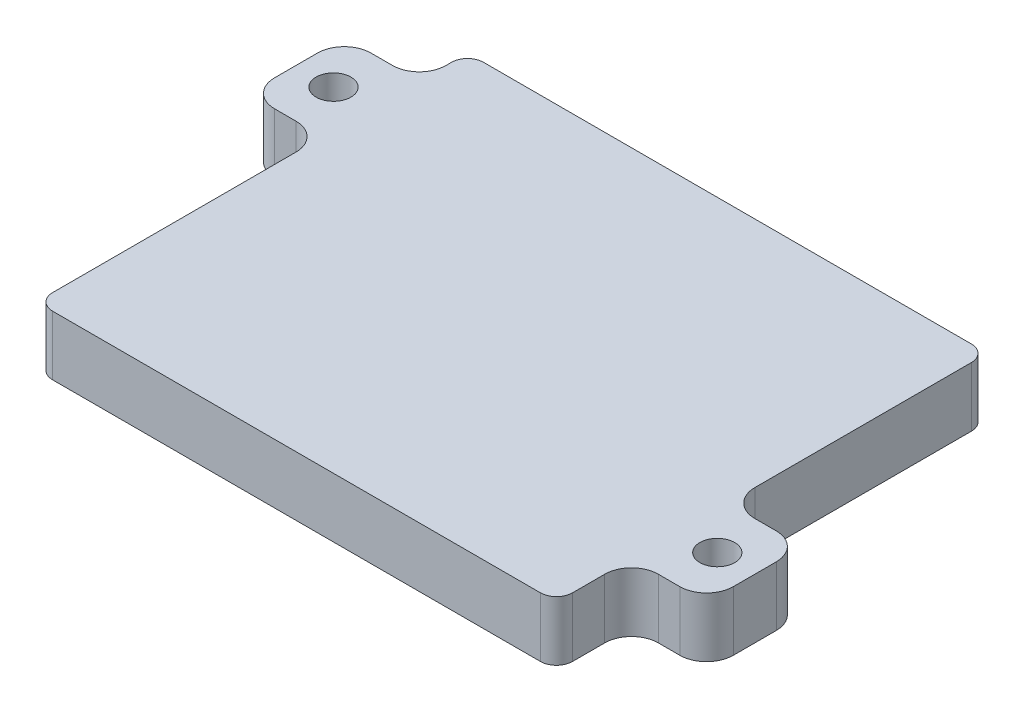
SolidWorks part; units mm, degrees
ref_plane "Front Plane" through (0, 0, 0) normal (0, 0, 1) x (1, 0, 0)
ref_plane "Top Plane" through (0, 0, 0) normal (0, 1, 0) x (1, 0, 0)
ref_plane "Right Plane" through (0, 0, 0) normal (1, 0, 0) x (0, 0, -1)
sketch "Sketch1" plane through (0, 0, 0) normal (0, 1, 0) x (1, 0, 0)
  line L1 (-45.0661, 38.3957) -> (51.9339, 38.3957)
  line L2 (-45.0661, 38.3957) -> (-45.0661, -42.0055)
  line L3 (-45.0661, -42.0055) -> (51.9339, -42.0055)
  line L4 (51.9339, 38.3957) -> (51.9339, -42.0055)
extrude "Boss-Extrude1" add sketch "Sketch1" along normal blind 12.6
sketch "Sketch3" plane through (0, 12.6, 0) normal (0, 1, 0) x (1, 0, 0)
  line L4 (-41.3661, 31.8316) -> (-41.3661, -34.1684)
  line L5 (-39.8661, -35.6684) -> (46.1339, -35.6684)
  line L6 (47.6339, -34.1684) -> (47.6339, 31.8316)
  line L7 (46.1339, 33.3316) -> (-39.8661, 33.3316)
  arc A4 (-41.3661, -34.1684) -> (-39.8661, -35.6684) centre (-39.8661, -34.1684) ccw
  arc A5 (46.1339, -35.6684) -> (47.6339, -34.1684) centre (46.1339, -34.1684) ccw
  arc A6 (47.6339, 31.8316) -> (46.1339, 33.3316) centre (46.1339, 31.8316) ccw
  arc A7 (-39.8661, 33.3316) -> (-41.3661, 31.8316) centre (-39.8661, 31.8316) ccw
extrude "Cut-Extrude2" cut sketch "Sketch3" against normal blind 10 from offset 5 offset against normal yes
sketch "Sketch6" plane through (0, 0, 0) normal (0, -1, 0) x (1, 0, 0)
  line L5 (51.9339, -38.3957) -> (-45.0661, -38.3957)
  line L6 (51.9339, -38.3957) -> (51.9339, 42.0055)
  line L7 (51.9339, 42.0055) -> (-45.0661, 42.0055)
  line L8 (-39.8661, -34.3316) -> (46.1339, -34.3316)
  line L9 (-42.3661, 34.1684) -> (-42.3661, -31.8316)
  line L10 (46.1339, 36.6684) -> (-39.8661, 36.6684)
  line L11 (48.6339, -31.8316) -> (48.6339, 34.1684)
  line L12 (-39.8661, -34.3316) -> (46.1339, -34.3316)
  line L13 (-42.3661, 34.1684) -> (-42.3661, -31.8316)
  line L14 (46.1339, 36.6684) -> (-39.8661, 36.6684)
  line L15 (48.6339, -31.8316) -> (48.6339, 34.1684)
  line L16 (-45.0661, -38.3957) -> (-45.0661, 42.0055)
  arc A8 (-42.3661, -31.8316) -> (-39.8661, -34.3316) centre (-39.8661, -31.8316) ccw
  arc A9 (-39.8661, 36.6684) -> (-42.3661, 34.1684) centre (-39.8661, 34.1684) ccw
  arc A10 (48.6339, 34.1684) -> (46.1339, 36.6684) centre (46.1339, 34.1684) ccw
  arc A11 (46.1339, -34.3316) -> (48.6339, -31.8316) centre (46.1339, -31.8316) ccw
  arc A12 (-42.3661, -31.8316) -> (-39.8661, -34.3316) centre (-39.8661, -31.8316) ccw
  arc A13 (-39.8661, 36.6684) -> (-42.3661, 34.1684) centre (-39.8661, 34.1684) ccw
  arc A14 (48.6339, 34.1684) -> (46.1339, 36.6684) centre (46.1339, 34.1684) ccw
  arc A15 (46.1339, -34.3316) -> (48.6339, -31.8316) centre (46.1339, -31.8316) ccw
  dimension "D1" = 1
extrude "Cut-Extrude3" cut sketch "Sketch6" against normal blind 1.5
fillet "Fillet1" radius 3 4 edges at (51.9339, 7.05, -38.3957) (-45.0661, 7.05, -38.3957) (-45.0661, 7.05, 42.0055) (51.9339, 7.05, 42.0055)
sketch "Sketch7" plane through (-45.0661, 0, 0) normal (-1, 0, 0) x (0, 0, 1)
  line L0 (-35.3957, 12.6) -> (39.0055, 12.6) construction
  line L2 (39.0055, 1.5) -> (-35.3957, 1.5) construction
  line L3 (-35.3957, 12.6) -> (-35.3957, 1.5) construction
  line L4 (-29.3957, 12.6) -> (-11.3957, 12.6)
  line L5 (-29.3957, 12.6) -> (-29.3957, 1.5)
  line L6 (-29.3957, 1.5) -> (-11.3957, 1.5)
  line L7 (-11.3957, 12.6) -> (-11.3957, 1.5)
  line L8 (-29.3957, 12.6) -> (-11.3957, 1.5) construction
  line L9 (-29.3957, 1.5) -> (-11.3957, 12.6) construction
  point P0 (-13.2411, 6.1558)
  point P6 (-20.3957, 7.05)
  dimension "D1" = 18
  dimension "D2" = 15
sketch "Sketch8" plane through (51.9339, 0, 0) normal (1, 0, 0) x (0, 0, -1)
  line L0 (-39.0055, 12.6) -> (35.3957, 12.6) construction
  line L2 (35.3957, 1.5) -> (-39.0055, 1.5) construction
  line L3 (-39.0055, 12.6) -> (-39.0055, 1.5) construction
  line L4 (-28.0055, 12.6) -> (-10.0055, 12.6)
  line L5 (-28.0055, 12.6) -> (-28.0055, 1.5)
  line L6 (-28.0055, 1.5) -> (-10.0055, 1.5)
  line L7 (-10.0055, 12.6) -> (-10.0055, 1.5)
  line L8 (-28.0055, 12.6) -> (-10.0055, 1.5) construction
  line L9 (-28.0055, 1.5) -> (-10.0055, 12.6) construction
  point P0 (-19.2369, 6.2426)
  point P6 (-19.0055, 7.05)
  dimension "D1" = 18
  dimension "D2" = 20
extrude "Boss-Extrude2" add sketch "Sketch7" along normal blind 14
extrude "Boss-Extrude3" add sketch "Sketch8" along normal blind 14
fillet "Fillet2" radius 5 8 edges at (-45.0661, 7.05, -11.3957) (-59.0661, 7.05, -11.3957) (-45.0661, 7.05, -29.3957) (-59.0661, 7.05, -29.3957) (51.9339, 7.05, 28.0055) (51.9339, 7.05, 10.0055) (65.9339, 7.05, 28.0055) (65.9339, 7.05, 10.0055)
sketch "Sketch9" plane through (0, 12.6, 0) normal (0, 1, 0) x (1, 0, 0)
  line L0 (65.9339, -19.0055) -> (-67.2596, -19.0055) construction
  line L1 (65.9339, -15.0055) -> (65.9339, -23.0055) construction
  line L2 (-59.0661, 16.3957) -> (-59.0661, 24.3957) construction
  line L3 (-59.0661, 20.3957) -> (-8.5439, 20.3957) construction
  circle A0 centre (58.9339, -19.0055) radius 3.25
  circle A1 centre (-52.0661, 20.3957) radius 3.25
  point P10 (0, 0)
  point P11 (0, 0)
  point P12 (-52.0661, 20.3957)
  dimension "D3" = 6.5
  dimension "D4" = 6.5
  dimension "D1" = 7
  dimension "D2" = 7
extrude "Cut-Extrude4" cut sketch "Sketch9" against normal through all
sketch "Sketch10" plane through (0, 0, 0) normal (0, 1, 0) x (1, 0, 0)
  line L4 (46.1339, 33.3316) -> (-39.8661, 33.3316)
  line L5 (-41.3661, 31.8316) -> (-41.3661, -34.1684)
  line L6 (-39.8661, -35.6684) -> (46.1339, -35.6684)
  line L7 (47.6339, -34.1684) -> (47.6339, 31.8316)
  line L8 (46.1339, 33.3316) -> (-39.8661, 33.3316)
  line L9 (-41.3661, 31.8316) -> (-41.3661, -34.1684)
  line L10 (-39.8661, -35.6684) -> (46.1339, -35.6684)
  line L11 (47.6339, -34.1684) -> (47.6339, 31.8316)
  line L12 (-59.0661, 24.3957) -> (-59.0661, 16.3957)
  line L13 (-54.0661, 11.3957) -> (-50.0661, 11.3957)
  line L14 (-45.0661, 6.3957) -> (-45.0661, -39.0055)
  line L15 (-42.0661, -42.0055) -> (48.9339, -42.0055)
  line L16 (51.9339, -39.0055) -> (51.9339, -33.0055)
  line L17 (56.9339, -28.0055) -> (60.9339, -28.0055)
  line L18 (65.9339, -23.0055) -> (65.9339, -15.0055)
  line L19 (60.9339, -10.0055) -> (56.9339, -10.0055)
  line L20 (51.9339, -5.0055) -> (51.9339, 35.3957)
  line L21 (48.9339, 38.3957) -> (-42.0661, 38.3957)
  line L22 (-45.0661, 35.3957) -> (-45.0661, 34.3957)
  line L23 (-50.0661, 29.3957) -> (-54.0661, 29.3957)
  line L24 (-59.0661, 24.3957) -> (-59.0661, 16.3957)
  line L25 (-54.0661, 11.3957) -> (-50.0661, 11.3957)
  line L26 (-45.0661, 6.3957) -> (-45.0661, -39.0055)
  line L27 (-42.0661, -42.0055) -> (48.9339, -42.0055)
  line L28 (51.9339, -39.0055) -> (51.9339, -33.0055)
  line L29 (56.9339, -28.0055) -> (60.9339, -28.0055)
  line L30 (65.9339, -23.0055) -> (65.9339, -15.0055)
  line L31 (60.9339, -10.0055) -> (56.9339, -10.0055)
  line L32 (51.9339, -5.0055) -> (51.9339, 35.3957)
  line L33 (48.9339, 38.3957) -> (-42.0661, 38.3957)
  line L34 (-45.0661, 35.3957) -> (-45.0661, 34.3957)
  line L35 (-50.0661, 29.3957) -> (-54.0661, 29.3957)
  line L36 (46.1339, 34.3316) -> (-39.8661, 34.3316)
  line L37 (48.6339, -34.1684) -> (48.6339, 31.8316)
  line L38 (-39.8661, -36.6684) -> (46.1339, -36.6684)
  line L39 (-42.3661, 31.8316) -> (-42.3661, -34.1684)
  line L40 (46.1339, 34.3316) -> (-39.8661, 34.3316)
  line L41 (48.6339, -34.1684) -> (48.6339, 31.8316)
  line L42 (-39.8661, -36.6684) -> (46.1339, -36.6684)
  line L43 (-42.3661, 31.8316) -> (-42.3661, -34.1684)
  circle A0 centre (-52.0661, 20.3957) radius 3.25 construction
  circle A1 centre (58.9339, -19.0055) radius 3.25 construction
  circle A2 centre (-52.0661, 20.3957) radius 3.25
  circle A3 centre (58.9339, -19.0055) radius 3.25
  arc A8 (-39.8661, 33.3316) -> (-41.3661, 31.8316) centre (-39.8661, 31.8316) ccw
  arc A9 (-41.3661, -34.1684) -> (-39.8661, -35.6684) centre (-39.8661, -34.1684) ccw
  arc A10 (46.1339, -35.6684) -> (47.6339, -34.1684) centre (46.1339, -34.1684) ccw
  arc A11 (47.6339, 31.8316) -> (46.1339, 33.3316) centre (46.1339, 31.8316) ccw
  arc A12 (-59.0661, 16.3957) -> (-54.0661, 11.3957) centre (-54.0661, 16.3957) ccw
  arc A13 (-45.0661, 6.3957) -> (-50.0661, 11.3957) centre (-50.0661, 6.3957) ccw
  arc A14 (-45.0661, -39.0055) -> (-42.0661, -42.0055) centre (-42.0661, -39.0055) ccw
  arc A15 (48.9339, -42.0055) -> (51.9339, -39.0055) centre (48.9339, -39.0055) ccw
  arc A16 (56.9339, -28.0055) -> (51.9339, -33.0055) centre (56.9339, -33.0055) ccw
  arc A17 (60.9339, -28.0055) -> (65.9339, -23.0055) centre (60.9339, -23.0055) ccw
  arc A18 (65.9339, -15.0055) -> (60.9339, -10.0055) centre (60.9339, -15.0055) ccw
  arc A19 (51.9339, -5.0055) -> (56.9339, -10.0055) centre (56.9339, -5.0055) ccw
  arc A20 (51.9339, 35.3957) -> (48.9339, 38.3957) centre (48.9339, 35.3957) ccw
  arc A21 (-42.0661, 38.3957) -> (-45.0661, 35.3957) centre (-42.0661, 35.3957) ccw
  arc A22 (-50.0661, 29.3957) -> (-45.0661, 34.3957) centre (-50.0661, 34.3957) ccw
  arc A23 (-54.0661, 29.3957) -> (-59.0661, 24.3957) centre (-54.0661, 24.3957) ccw
  arc A24 (-59.0661, 16.3957) -> (-54.0661, 11.3957) centre (-54.0661, 16.3957) ccw
  arc A25 (-45.0661, 6.3957) -> (-50.0661, 11.3957) centre (-50.0661, 6.3957) ccw
  arc A26 (-45.0661, -39.0055) -> (-42.0661, -42.0055) centre (-42.0661, -39.0055) ccw
  arc A27 (48.9339, -42.0055) -> (51.9339, -39.0055) centre (48.9339, -39.0055) ccw
  arc A28 (56.9339, -28.0055) -> (51.9339, -33.0055) centre (56.9339, -33.0055) ccw
  arc A29 (60.9339, -28.0055) -> (65.9339, -23.0055) centre (60.9339, -23.0055) ccw
  arc A30 (65.9339, -15.0055) -> (60.9339, -10.0055) centre (60.9339, -15.0055) ccw
  arc A31 (51.9339, -5.0055) -> (56.9339, -10.0055) centre (56.9339, -5.0055) ccw
  arc A32 (51.9339, 35.3957) -> (48.9339, 38.3957) centre (48.9339, 35.3957) ccw
  arc A33 (-42.0661, 38.3957) -> (-45.0661, 35.3957) centre (-42.0661, 35.3957) ccw
  arc A34 (-50.0661, 29.3957) -> (-45.0661, 34.3957) centre (-50.0661, 34.3957) ccw
  arc A35 (-54.0661, 29.3957) -> (-59.0661, 24.3957) centre (-54.0661, 24.3957) ccw
  arc A36 (-39.8661, 33.3316) -> (-41.3661, 31.8316) centre (-39.8661, 31.8316) ccw
  arc A37 (-41.3661, -34.1684) -> (-39.8661, -35.6684) centre (-39.8661, -34.1684) ccw
  arc A38 (46.1339, -35.6684) -> (47.6339, -34.1684) centre (46.1339, -34.1684) ccw
  arc A39 (47.6339, 31.8316) -> (46.1339, 33.3316) centre (46.1339, 31.8316) ccw
  arc A40 (-39.8661, 34.3316) -> (-42.3661, 31.8316) centre (-39.8661, 31.8316) ccw
  arc A41 (48.6339, 31.8316) -> (46.1339, 34.3316) centre (46.1339, 31.8316) ccw
  arc A42 (46.1339, -36.6684) -> (48.6339, -34.1684) centre (46.1339, -34.1684) ccw
  arc A43 (-42.3661, -34.1684) -> (-39.8661, -36.6684) centre (-39.8661, -34.1684) ccw
  arc A44 (-39.8661, 34.3316) -> (-42.3661, 31.8316) centre (-39.8661, 31.8316) ccw
  arc A45 (48.6339, 31.8316) -> (46.1339, 34.3316) centre (46.1339, 31.8316) ccw
  arc A46 (46.1339, -36.6684) -> (48.6339, -34.1684) centre (46.1339, -34.1684) ccw
  arc A47 (-42.3661, -34.1684) -> (-39.8661, -36.6684) centre (-39.8661, -34.1684) ccw
  dimension "D1" = 0
  dimension "D2" = 0
  dimension "D3" = 0
